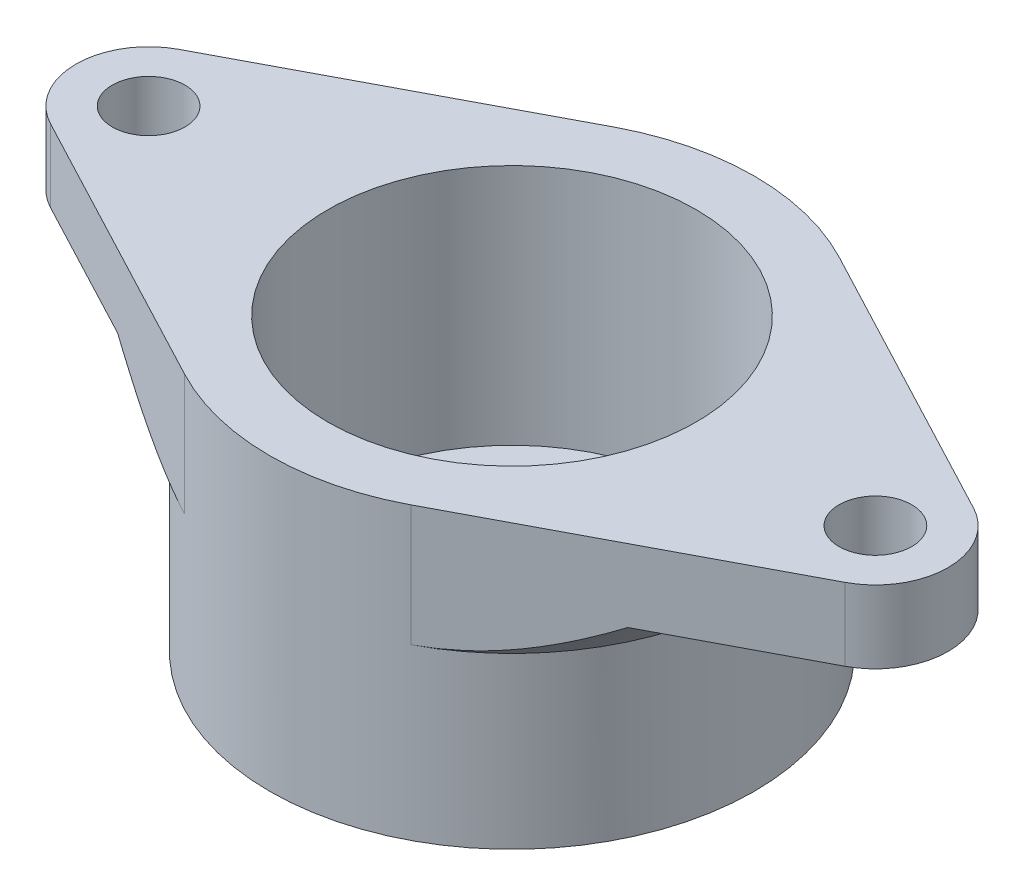
SolidWorks part; units mm, degrees
ref_plane "Alzado" through (0, 0, 0) normal (0, 0, 1) x (1, 0, 0)
ref_plane "Planta" through (0, 0, 0) normal (0, 1, 0) x (1, 0, 0)
ref_plane "Vista lateral" through (0, 0, 0) normal (1, 0, 0) x (0, 0, -1)
sketch "Croquis1" plane through (0, 0, 0) normal (0, 1, 0) x (1, 0, 0)
  circle A0 centre (0, 0) radius 6
  circle A1 centre (0, 0) radius 10
  dimension "D1" = 12
  dimension "D2" = 20
extrude "Saliente-Extruir1" add sketch "Croquis1" along normal blind 2
sketch "Croquis2" plane through (0, 2, 0) normal (0, 1, 0) x (1, 0, 0)
  circle A0 centre (0, 0) radius 7.6
  circle A1 centre (0, 0) radius 10
  dimension "D1" = 15.2
extrude "Saliente-Extruir2" add sketch "Croquis2" along normal blind 10
sketch "Croquis4" plane through (0, 12, 0) normal (0, 1, 0) x (1, 0, 0)
  line L0 (0, 0) -> (15, 0)
  line L1 (0, 0) -> (-15, 0)
  line L2 (-16.4, 2.6533) -> (-4.6667, 8.8443)
  line L3 (0, 0) -> (0, 2.6533) construction
  line L4 (-16.4, -2.6533) -> (-4.6667, -8.8443)
  line L5 (16.4, -2.6533) -> (4.6667, -8.8443)
  line L6 (16.4, 2.6533) -> (4.6667, 8.8443)
  circle A0 centre (-15, 0) radius 3
  circle A1 centre (-15, 0) radius 1.5
  circle A2 centre (0, 0) radius 10 construction
  circle A3 centre (0, 0) radius 10
  circle A4 centre (15, 0) radius 1.5
  circle A5 centre (15, 0) radius 3
  dimension "D3" = 6
  dimension "D4" = 3
  dimension "D2" = 15
extrude "Saliente-Extruir3" add sketch "Croquis4" against normal blind 3
chamfer "Chaflán1" distance 2 angle 45 2 edges at (10, 9, 0) (-10, 9, 0)
